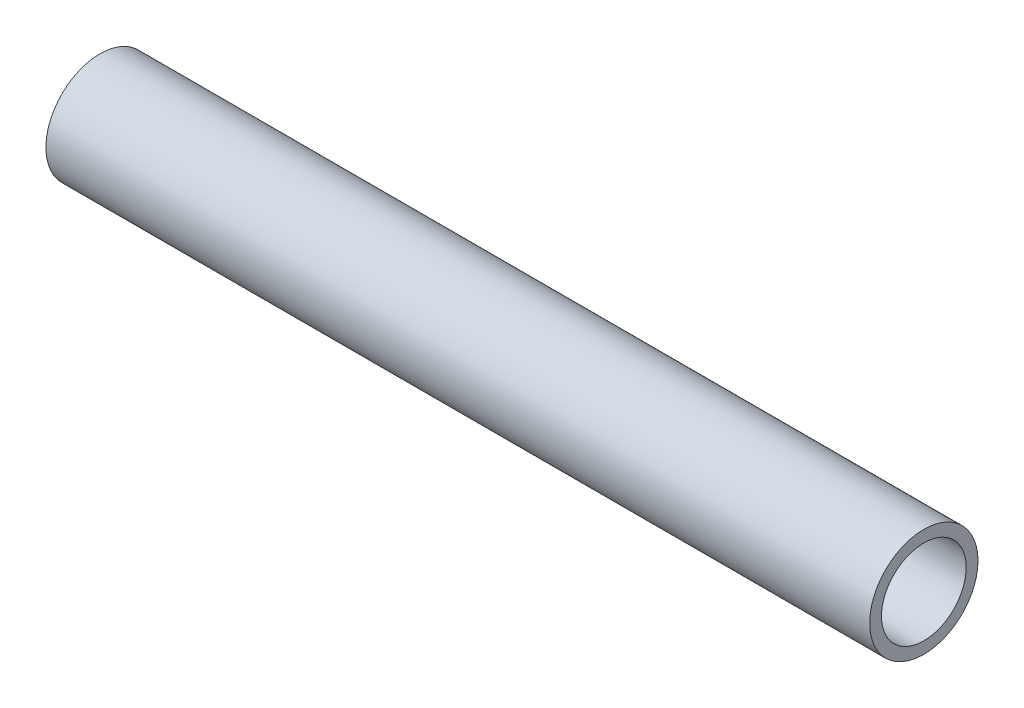
SolidWorks part; units mm, degrees
ref_plane "Front Plane" through (0, 0, 0) normal (0, 0, 1) x (1, 0, 0)
ref_plane "Top Plane" through (0, 0, 0) normal (0, 1, 0) x (1, 0, 0)
ref_plane "Right Plane" through (0, 0, 0) normal (1, 0, 0) x (0, 0, -1)
sketch "Sketch1" plane through (0, 0, 0) normal (1, 0, 0) x (0, 0, -1)
  circle A0 centre (0, 0) radius 16.7005
  circle A1 centre (0, 0) radius 13.0683
  dimension "D1" = 33.401
  dimension "D2" = 26.1366
extrude "Boss-Extrude1" add sketch "Sketch1" along normal blind 254
sketch "Sketch3" plane through (0, 0, 0) normal (0, 1, 0) x (1, 0, 0)
  line L0 (127, 16.7005) -> (127, -16.7005) construction
  line L1 (254, 16.7005) -> (0, 16.7005) construction
  line L2 (0, -16.7005) -> (254, -16.7005) construction
  circle A0 centre (127, 0) radius 3.2639
  dimension "D1" = 6.5278
extrude "Cut-Extrude2" [suppressed] cut sketch "Sketch3" against normal through all both and the other way through all
ref_axis "Axis1" through (254, 0, 0) along (-1, 0, 0)
ref_plane "Plane1" through (0, 0, 0) normal (0, 0.8192, -0.5736) x (-1, 0, 0)
sketch "Sketch4" plane through (0, 0, 0) normal (0, 0.8192, -0.5736) x (-1, 0, 0)
  line L0 (-254, 0) -> (-203.2, 0) construction
  line L1 (-254, 16.7005) -> (-254, -16.7005) construction
  line L2 (-254, 0) -> (0, 0) construction
  line L3 (0, 0) -> (-50.8, 0) construction
  circle A0 centre (-203.2, 0) radius 3.2639
  circle A1 centre (-50.8, 0) radius 3.2639
  dimension "D2" = 6.5278
  dimension "D1" = 50.8
extrude "Cut-Extrude3" [suppressed] cut sketch "Sketch4" against normal through all both and the other way through all
sketch "Sketch5" plane through (254, 0, 0) normal (1, 0, 0) x (0, 0, -1)
  circle A0 centre (0, 0) radius 16.7005 construction
  circle A1 centre (0, 0) radius 16.7005
extrude "Cut-Extrude4" [suppressed] cut sketch "Sketch5" against normal blind 79.375
mirror "Mirror1" [suppressed] about plane through (0, 0, 0) normal (0, 0, 1)
sketch "Sketch7" plane through (0, 0, 0) normal (-1, 0, 0) x (0, 0, 1)
  circle A1 centre (0, 0) radius 16.7005
  circle A2 centre (0, 0) radius 16.7005
  dimension "D1" = 0
extrude "Cut-Extrude6" [suppressed] cut sketch "Sketch7" against normal blind 3.175
